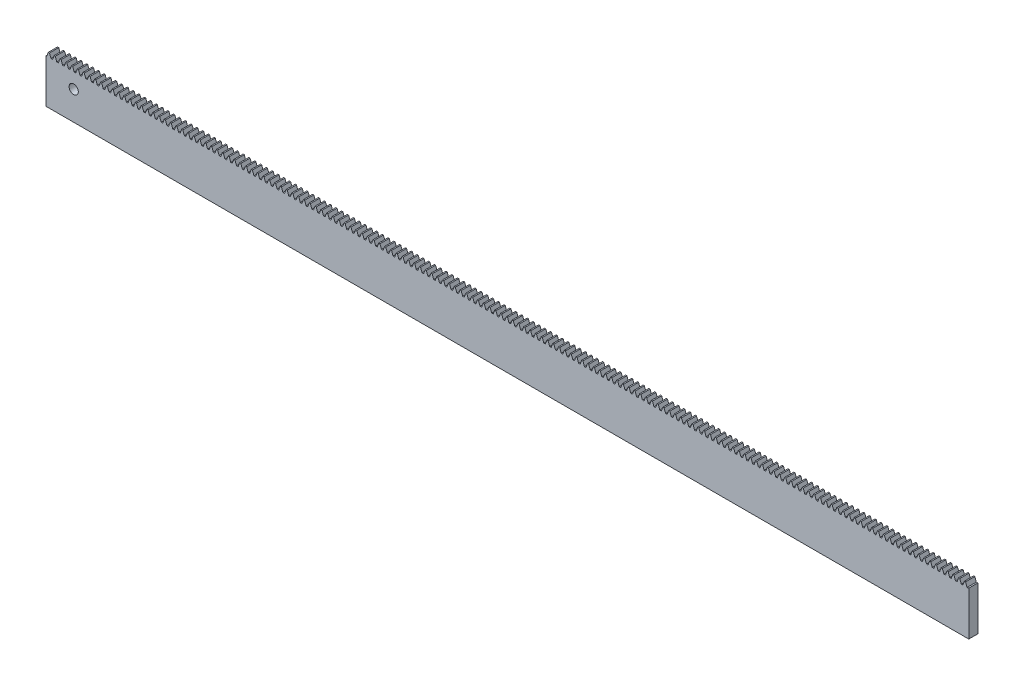
SolidWorks part; units mm, degrees
extrude "Blank" add sketch "BlankSke" against normal blind 10
sketch "BlankSke" plane through (0, 0, 0) normal (0, 0, 1) x (1, 0, 0)
  line L1 (0, 0) -> (1000, 0)
  line L2 (0, 0) -> (0, 52)
  line L3 (0, 52) -> (1000, 52)
  line L4 (1000, 0) -> (1000, 52)
  dimension "Length" = 1000
ref_plane "Plane1" through (0, 0, 0) normal (0, 0, 1) x (1, 0, 0)
ref_plane "Plane2" through (0, 0, 0) normal (0, 1, 0) x (1, 0, 0)
ref_plane "Plane3" through (0, 0, 0) normal (1, 0, 0) x (0, 0, -1)
sketch "HoldingSke" plane through (0, 0, 0) normal (0, 1, 0) x (1, 0, 0)
  line L0 (0, 0) -> (0.0696, 0.4951)
  line L1 (-15, 0) -> (100, 0) construction
  line L2 (0, 0) -> (-2.1039, 2.3779)
  line L3 (0, 0) -> (-11.863, 4.5341)
  line L4 (0, 0) -> (-8.1655, 2.8116)
  line L5 (0, 0) -> (-23.7986, -8.8762)
  line L6 (0, 0) -> (-10.5278, -7.1032)
  line L9 (-71.009, 38.7566) -> (868.6837, 380.7768)
  line L10 (-76.2, 4.3779) -> (-26.2, 4.3779)
  line L11 (0, 0) -> (-10, 0)
  line L12 (-76.2, 101.6) -> (-76.133, 101.6)
  line L13 (24.9733, 27.94) -> (52.9518, 28.4284)
  line L14 (24.9733, 27.94) -> (24.9743, 27.94)
  line L15 (24.9733, 27.94) -> (100.4006, 29.5858)
  circle A0 centre (0, 0) radius 19.05
  circle A1 centre (0, 0) radius 25
  circle A2 centre (0, 0) radius 12.7
  dimension "Num_teeth" = 161
  dimension "Width" = 10
  dimension "Length" = 1000
  dimension "Pitch_height" = 50
sketch "TooCutSkeIll" plane through (0, 0, 0) normal (0, 0, 1) x (1, 0, 0)
  line L0 (-2.4806, 51.9474) -> (-0.9819, 47.8296)
  line L1 (-0.5111, 47.5) -> (0.5111, 47.5)
  line L2 (0.9819, 47.8296) -> (2.4806, 51.9474)
  line L3 (1000, 52) -> (0, 52) construction
  line L4 (0, 0) -> (0, 64.897) construction
  line L5 (-13.208, 50) -> (12.954, 50) construction
  line L6 (0, 0) -> (1000, 0) construction
  line L7 (1.7718, 50) -> (1.7718, 48.7463) construction
  line L8 (-1.7718, 50) -> (-1.7718, 48.7463) construction
  line L9 (2.5558, 52) -> (2.5558, 52.0254)
  line L10 (-2.5558, 52) -> (-2.5558, 52.0254)
  line L11 (-2.5558, 52.0254) -> (2.5558, 52.0254)
  arc A0 (0.5111, 47.5) -> (0.9819, 47.8296) centre (0.5111, 48.001) ccw
  arc A1 (-0.9819, 47.8296) -> (-0.5111, 47.5) centre (-0.5111, 48.001) ccw
  arc A2 (2.5558, 52) -> (2.4806, 51.9474) centre (2.5558, 51.92) ccw
  arc A3 (-2.4806, 51.9474) -> (-2.5558, 52) centre (-2.5558, 51.92) ccw
  dimension "Addendum_plus" = 2.0254
  dimension "Pitch_height" = 50
  dimension "Pressure_angle" = 20
  dimension "Gap_width" = 3.5436
  dimension "Dedendum" = 2.5
extrude "ToothCutIll" [suppressed] cut sketch "TooCutSkeIll" against normal through all
sketch "TooCutSkeSim" plane through (0, 0, 0) normal (0, 0, 1) x (1, 0, 0)
  line L0 (0.8619, 47.5) -> (-0.8619, 47.5)
  line L1 (2.509, 52.0254) -> (0.8619, 47.5)
  line L2 (0, 17.4625) -> (0, 53.467) construction
  line L3 (2.509, 52.0254) -> (-2.509, 52.0254)
  line L6 (-2.509, 52.0254) -> (-0.8619, 47.5)
  line L9 (-1.7718, 50) -> (1.7718, 50) construction
  line L10 (0, 0) -> (1000, 0) construction
  line L11 (1.7718, 50) -> (1.7718, 53.467) construction
  line L12 (-1.7718, 50) -> (-1.7718, 53.467) construction
  dimension "Addendum_plus" = 2.0254
  dimension "Pitch_height" = 50
  dimension "Pressure_angle" = 20
  dimension "Gap_width" = 3.5436
  dimension "Dedendum" = 2.5
extrude "ToothCutSim" cut sketch "TooCutSkeSim" against normal through all
pattern_linear "TeethCuts" count 161 spacing 6.2832 along (1, 0, 0) of "ToothCutIll", "ToothCutSim"
sketch "Эскиз1" plane through (0, 0, 0) normal (0, 0, 1) x (1, 0, 0)
  line L0 (35.1994, 52) -> (33.9157, 52) construction
  line L1 (0, 47.5) -> (0, 0) construction
  line L2 (495.5098, 47.5) -> (497.2335, 47.5) construction
  circle A0 centre (30, 31) radius 5
  dimension "D2" = 10
  dimension "D1" = 21
  dimension "D3" = 30
extrude "Вырез-Вытянуть1" cut sketch "Эскиз1" against normal through all
equation "' \"Module@HoldingSke\" = 6.35"
equation "' \"Num_teeth@HoldingSke\" = 12"
equation "' \"Ap@HoldingSke\" =  20"
equation "' \"Ap@HoldingSke\" = 20"
equation "' \"Width@HoldingSke\" = 0.25 * 25.4"
equation "' \"Show_teeth@HoldingSke\" = 500"
equation "' \"Backlash@HoldingSke\" = 0.009 * 25.4"
equation "' \"Addendum_fac@HoldingSke\" = 1.0"
equation "' \"Dedendum_fac@HoldingSke\" = 1.25"
equation "' \"Dedendum_add@HoldingSke\" = 0.00005 * 25.4"
equation "' \"Clearance_fac@HoldingSke\" = 0.25"
equation "' \"Pitch_height@HoldingSke\" = 1 * 25.4"
equation "' \"Length@HoldingSke\" = 4.71 * 25.4"
equation "\"Pitch@HoldingSke\" = 1 / \"Module@HoldingSke\""
equation "\"MPH@HoldingSke\" = \"Dedendum_fac@HoldingSke\" / \"Pitch@HoldingSke\" + 2 * \"Dedendum_add@HoldingSke\" + 0.002 * 25.4"
equation "\"MPH@HoldingSke\" = ((sgn( \"MPH@HoldingSke\" - \"Pitch_height@HoldingSke\")+1)*( \"MPH@HoldingSke\" - \"Pitch_height@HoldingSke\"))/2 + \"Pitch_height@HoldingSke\""
equation "\"Blank_height@BlankSke\" = \"Pitch_height@HoldingSke\" + \"Addendum_fac@HoldingSke\"  / \"Pitch@HoldingSke\" "
equation "\"Length@BlankSke\" =  \"Length@HoldingSke\""
equation "\"Face_width@Blank\" = \"Width@HoldingSke\""
equation "\"Pressure_angle@TooCutSkeIll\" = \"Ap@HoldingSke\""
equation "\"Addendum_plus@TooCutSkeIll\" =  \"Addendum_fac@HoldingSke\"  / \"Pitch@HoldingSke\" + 0.001 *25.4"
equation "\"Dedendum@TooCutSkeIll\" = \"Dedendum_fac@HoldingSke\"  / \"Pitch@HoldingSke\""
equation "\"Pitch_height@TooCutSkeIll\" =  \"MPH@HoldingSke\""
equation "\"Gap_width@TooCutSkeIll\" = 3.14159265 / 2 / \"Pitch@HoldingSke\" + 6 * \"Backlash@HoldingSke\""
equation "\"Pressure_angle@TooCutSkeSim\" = \"Ap@HoldingSke\""
equation "\"Addendum_plus@TooCutSkeSim\" =  \"Addendum_fac@HoldingSke\"  / \"Pitch@HoldingSke\" + 0.001 * 25.4"
equation "\"Dedendum@TooCutSkeSim\" = \"Dedendum_fac@HoldingSke\"  / \"Pitch@HoldingSke\""
equation "\"Pitch_height@TooCutSkeSim\" =  \"MPH@HoldingSke\""
equation "\"Gap_width@TooCutSkeSim\" = 3.14159265 / 2 / \"Pitch@HoldingSke\" + 6 * \"Backlash@HoldingSke\""
equation "\"Root_fillet@TooCutSkeIll\" = \"Clearance_fac@HoldingSke\" / \"Pitch@HoldingSke\" + \"Dedendum_add@HoldingSke\""
equation "\"Break_rad@TooCutSkeIll\" = 0.02 / \"Pitch@HoldingSke\" * 2"
equation "\"Linear_pitch@TeethCuts\" = 3.14159265 / \"Pitch@HoldingSke\""
equation "\"Num_teeth@HoldingSke\" = int( ( \"Length@HoldingSke\" + 0 ) / (3.14159265 / \"Pitch@HoldingSke\")) + 0.9999  + 1"
equation " \"Num_teeth@TeethCuts\" = int( \"Show_teeth@HoldingSke\" ) + 1"
equation " \"Num_teeth@TeethCuts\" = ((sgn( \"Num_teeth@TeethCuts\" - \"Num_teeth@HoldingSke\" )-1)*( \"Num_teeth@TeethCuts\" - \"Num_teeth@HoldingSke\" ))/-2+ \"Num_teeth@HoldingSke\""
equation " \"Num_teeth@TeethCuts\" = ((sgn( \"Num_teeth@TeethCuts\" - 2.0)+1)*( \"Num_teeth@TeethCuts\" - 2.0))/2 +2.0"
